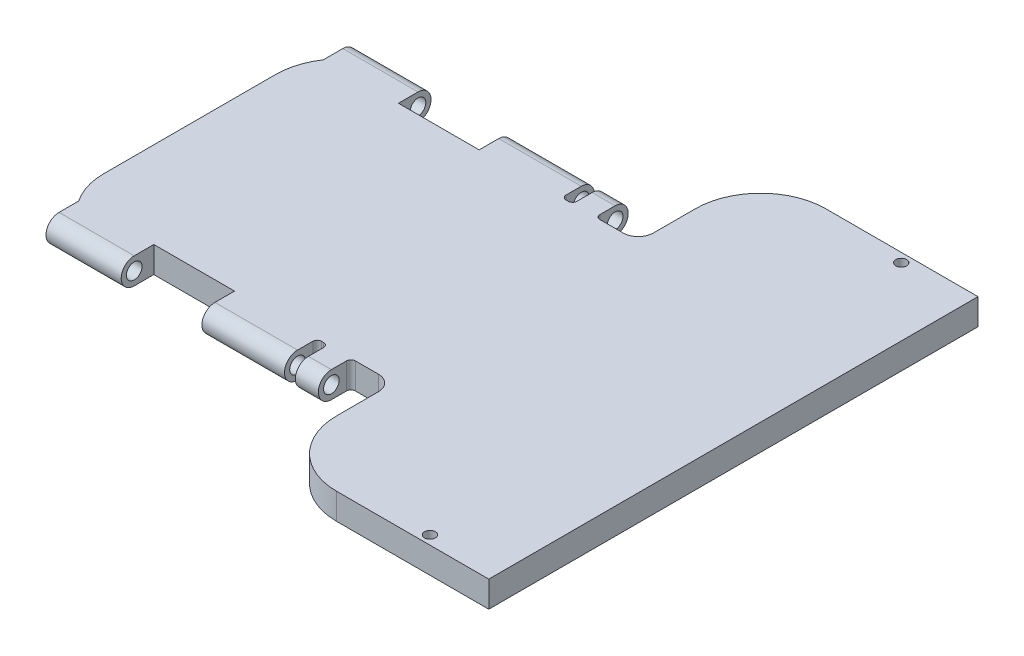
SolidWorks part; units mm, degrees
ref_plane "Front Plane" through (0, 0, 0) normal (0, 0, 1) x (1, 0, 0)
ref_plane "Top Plane" through (0, 0, 0) normal (0, 1, 0) x (1, 0, 0)
ref_plane "Right Plane" through (0, 0, 0) normal (1, 0, 0) x (0, 0, -1)
sketch "Sketch1" plane through (0, 0, 0) normal (0, 1, 0) x (1, 0, 0)
  line L0 (-120, -37.5) -> (-120, -75)
  line L1 (-120, 75) -> (0, 75)
  line L2 (-120, 75) -> (-120, 37.5)
  line L3 (-120, -75) -> (0, -75)
  line L5 (-120, 75) -> (0, 0) construction
  line L6 (0, 75) -> (0, -75)
  line L7 (-220, 37.5) -> (-120, 37.5)
  line L8 (-220, 37.5) -> (-220, -37.5)
  line L9 (-220, -37.5) -> (-120, -37.5)
  line L11 (-220, 37.5) -> (-120, -37.5) construction
  line L12 (-220, -37.5) -> (-120, 37.5) construction
  line L13 (-237.7651, 0) -> (0, 0) construction
  line L14 (0, 88.8927) -> (0, -90.7354) construction
  point P0 (0, 0)
  point P6 (-170, 0)
  dimension "D1" = 100
  dimension "D2" = 75
  dimension "D3" = 120
  dimension "D4" = 150
extrude "Boss-Extrude1" add sketch "Sketch1" along normal blind 8
ref_plane "Plane1" through (-170, 0, 0) normal (-1, 0, 0) x (0, 0, 1)
sketch "Sketch4" plane through (-170, 0, 0) normal (-1, 0, 0) x (0, 0, 1)
  line L0 (37.5, 8) -> (43.5, 8)
  line L1 (37.5, 0) -> (43.5, 0)
  line L2 (37.5, 8) -> (37.5, 0)
  line L3 (0, 17.6181) -> (0, -10.735) construction
  line L4 (-37.5, 0) -> (-43.5, 0)
  line L5 (-37.5, 8) -> (-37.5, 0)
  line L6 (-37.5, 8) -> (-43.5, 8)
  arc A0 (43.5, 0) -> (43.5, 8) centre (43.5, 4) ccw
  circle A1 centre (43.5, 4) radius 2.4
  circle A2 centre (-43.5, 4) radius 2.4
  arc A3 (-43.5, 0) -> (-43.5, 8) centre (-43.5, 4) cw
  dimension "D1" = 6
extrude "Boss-Extrude2" add sketch "Sketch4" along normal blind 46.584 and the other way blind 46.584
sketch "Sketch6" plane through (0, 0, 0) normal (1, 0, 0) x (0, 0, -1)
  line L0 (0, 15.0631) -> (0, -9.5042) construction
  line L1 (-75, 4) -> (0, 4) construction
  line L2 (-75, 8) -> (-75, 0) construction
  line L3 (-75, 8) -> (75, 8) construction
  line L4 (-60, 5.5) -> (-40, 5.5)
  line L5 (-60, 5.5) -> (-60, 2.5)
  line L6 (-60, 2.5) -> (-40, 2.5)
  line L7 (-40, 5.5) -> (-40, 2.5)
  line L8 (-60, 5.5) -> (-40, 2.5) construction
  line L9 (-60, 2.5) -> (-40, 5.5) construction
  line L10 (40, 5.5) -> (40, 2.5)
  line L11 (60, 5.5) -> (60, 2.5)
  line L12 (60, 2.5) -> (40, 2.5)
  line L13 (60, 5.5) -> (40, 5.5)
  point P7 (-50, 4)
  dimension "D1" = 2.5
  dimension "D2" = 15
  dimension "D3" = 20
extrude "Boss-Extrude3" add sketch "Sketch6" along normal blind 30
sketch "Sketch7" plane through (0, 5.5, 0) normal (0, 1, 0) x (1, 0, 0)
  line L0 (30, 60) -> (30, 40) construction
  line L1 (-120, -75) -> (0, -75) construction
  line L3 (0, -50) -> (30, -50) construction
  line L4 (0, -40) -> (0, -60) construction
  line L5 (30, -40) -> (30, -60) construction
  circle A0 centre (22.5, 50) radius 2
  circle A1 centre (22.5, -50) radius 2
  dimension "D1" = 7.5
  dimension "D2" = 25
extrude "Cut-Extrude2" cut sketch "Sketch7" against normal through all and the other way through all
sketch "Sketch8" plane through (0, 0, 0) normal (1, 0, 0) x (0, 0, -1)
  line L0 (0, 8) -> (0, 0) construction
  line L1 (-75, 8) -> (75, 8) construction
  line L3 (-20, 5.5) -> (20, 5.5)
  line L4 (-20, 5.5) -> (-20, 2.5)
  line L5 (-20, 2.5) -> (20, 2.5)
  line L6 (20, 5.5) -> (20, 2.5)
  line L7 (-20, 5.5) -> (20, 2.5) construction
  line L8 (-20, 2.5) -> (20, 5.5) construction
  point P5 (0, 4)
  dimension "D1" = 2.5
  dimension "D2" = 40
extrude "Cut-Extrude3" cut sketch "Sketch8" against normal blind 40
sketch "Sketch9" plane through (0, 8, 0) normal (0, 1, 0) x (1, 0, 0)
  line L0 (0, -75) -> (0, 75) construction
  circle A0 centre (-32.5, 0) radius 2
  dimension "D1" = 32.5
extrude "Cut-Extrude4" cut sketch "Sketch9" against normal blind 40
fillet "Fillet1" radius 20 4 edges at (-220, 4, -37.5) (-220, 4, 37.5) (-120, 4, -75) (-120, 4, 75)
sketch "Sketch10" plane through (0, 8, 0) normal (0, 1, 0) x (1, 0, 0)
  line L3 (0, 69.5) -> (-100, 69.5)
  line L4 (0, 75) -> (-100, 75)
  line L5 (0, 75) -> (-100, 75)
  line L6 (-120, 55) -> (-114.5, 55)
  line L8 (0, 75) -> (100, 75)
  line L9 (120, 55) -> (114.5, 55)
  line L10 (0, 69.5) -> (100, 69.5)
  line L11 (-88.6453, 0) -> (73.4089, 0) construction
  line L12 (0, -75) -> (100, -75)
  line L13 (120, -55) -> (114.5, -55)
  line L14 (0, -69.5) -> (100, -69.5)
  line L15 (0, -69.5) -> (-100, -69.5)
  line L16 (-120, -55) -> (-114.5, -55)
  line L17 (0, -75) -> (-100, -75)
  arc A2 (-100, 69.5) -> (-114.5, 55) centre (-100, 55) ccw
  arc A3 (-100, 75) -> (-120, 55) centre (-100, 55) ccw
  arc A4 (-100, 75) -> (-120, 55) centre (-100, 55) ccw
  arc A5 (100, 75) -> (120, 55) centre (100, 55) cw
  arc A6 (100, 69.5) -> (114.5, 55) centre (100, 55) cw
  arc A7 (100, -75) -> (120, -55) centre (100, -55) ccw
  arc A8 (100, -69.5) -> (114.5, -55) centre (100, -55) ccw
  arc A9 (-100, -69.5) -> (-114.5, -55) centre (-100, -55) cw
  arc A10 (-100, -75) -> (-120, -55) centre (-100, -55) cw
  dimension "D1" = 0
  dimension "D2" = 5.5
sketch "Sketch17" plane through (0, 8, 0) normal (0, 1, 0) x (1, 0, 0)
  line L1 (-100, 75) -> (-100, 69.5) construction
  line L2 (-100, 72.25) -> (0, 72.25) construction
  line L3 (0, -75) -> (0, 75) construction
  line L4 (0, 0) -> (-128.8243, 0) construction
  circle A0 centre (-75, 72.25) radius 1.5
  circle A1 centre (-25, 72.25) radius 1.5
  circle A2 centre (-25, -72.25) radius 1.5
  circle A3 centre (-75, -72.25) radius 1.5
  dimension "D1" = 25
  dimension "D2" = 25
extrude "Cut-Extrude10" cut sketch "Sketch17" against normal blind 25
scale "Scale1" scale about centroid uniform scaling yes scale factor 1.5
sketch "Sketch18" plane through (0, 10, 0) normal (0, 1, 0) x (1, 0, 0)
  line L0 (-132.1126, -56.25) -> (-132.1126, -82.5) construction
  line L1 (-32.1126, 151.8559) -> (160.5236, 151.8559)
  line L2 (-32.1126, 151.8559) -> (-32.1126, -145.6636)
  line L3 (-32.1126, -145.6636) -> (160.5236, -145.6636)
  line L4 (160.5236, 151.8559) -> (160.5236, -145.6636)
  dimension "D1" = 100
extrude "Cut-Extrude11" cut sketch "Sketch18" against normal through all
sketch "Sketch19" plane through (0, 0, 112.5) normal (0, 0, 1) x (1, 0, 0)
  line L0 (-137.2366, 4) -> (-164.8092, 4) construction
  line L1 (-137.2366, -2) -> (-137.2366, 10) construction
  line L2 (-137.2366, -2) -> (-276.9885, -2) construction
  line L3 (-167.3092, 10) -> (-162.3092, 10)
  line L4 (-167.3092, 10) -> (-167.3092, -2)
  line L5 (-167.3092, -2) -> (-162.3092, -2)
  line L6 (-162.3092, 10) -> (-162.3092, -2)
  line L7 (-167.3092, 10) -> (-162.3092, -2) construction
  line L8 (-167.3092, -2) -> (-162.3092, 10) construction
  dimension "D1" = 27.5726
  dimension "D2" = 5
extrude "Cut-Extrude12" cut sketch "Sketch19" against normal up to vertex (56.25 mm away) up to point (-137.2366, 10, 56.25)
mirror "Mirror2" about plane through (0, 0, 0) normal (0, 0, 1) of "Cut-Extrude12"
sketch "Sketch20" plane through (0, 10, 0) normal (0, 1, 0) x (1, 0, 0)
  line L0 (-167.3092, -60.75) -> (-205.9068, -60.75) construction
  line L2 (-167.3092, -56.25) -> (-167.3092, -65.25) construction
  line L3 (-162.3092, -56.25) -> (-167.3092, -56.25) construction
  line L4 (-205.9068, -56.25) -> (-240.9068, -56.25)
  line L5 (-205.9068, -56.25) -> (-205.9068, -76.9988)
  line L6 (-205.9068, -76.9988) -> (-240.9068, -76.9988)
  line L7 (-240.9068, -56.25) -> (-240.9068, -76.9988)
  line L8 (-167.3092, -63.8038) -> (-151.7407, -63.8038) construction
  line L10 (-151.7407, -56.25) -> (-136.2091, -56.25)
  line L11 (-151.7407, -56.25) -> (-151.7407, -73.1043)
  line L12 (-151.7407, -73.1043) -> (-136.2091, -73.1043)
  line L13 (-136.2091, -56.25) -> (-136.2091, -73.1043)
  dimension "D1" = 38.5976
  dimension "D2" = 35
extrude "Cut-Extrude13" cut sketch "Sketch20" against normal through all
fillet "Fillet2" radius 2 5 edges at (-151.7407, 4, 56.25) (-167.3092, 4, 56.25) (-162.3092, 4, 56.25) (-240.9068, 4, 56.25) (-205.9068, 4, 56.25)
mirror "Mirror3" about plane through (0, 0, 0) normal (0, 0, 1) of "Cut-Extrude13"
fillet "Fillet3" radius 7 2 edges at (-132.1126, 4, 56.25) (-132.1126, 4, -56.25)
fillet "Fillet4" radius 2 5 edges at (-151.7407, 4, -56.25) (-167.3092, 4, -56.25) (-162.3092, 4, -56.25) (-240.9068, 4, -56.25) (-205.9068, 4, -56.25)
scale "Scale2" scale about centroid uniform scaling yes scale factor 0.8
sketch "Sketch21" plane through (0, 8.8, 0) normal (0, 1, 0) x (1, 0, 0)
  circle A0 centre (-79.4935, 86.7) radius 1.8
  circle A1 centre (-79.4935, -86.7) radius 1.8
extrude "Boss-Extrude4" add sketch "Sketch21" against normal up to surface (9.6 mm away) up to face at (-79.4935, 8.8, 84.9)
sketch "Sketch22" plane through (0, 8.8, 0) normal (0, 1, 0) x (1, 0, 0)
  line L0 (-109.4935, 90) -> (-109.4935, 83.4) construction
  line L1 (-109.4935, 83.4) -> (-53.4935, 83.4) construction
  line L2 (-53.4935, 90) -> (-53.4935, -90) construction
  line L3 (-109.4935, 86.7) -> (-53.4935, 86.7) construction
  line L4 (-109.4935, -86.7) -> (-53.4935, -86.7) construction
  line L6 (-253.4935, 0) -> (-53.4935, 0) construction
  line L7 (-253.4935, 31.5851) -> (-253.4935, -31.5851) construction
  line L8 (-109.4935, -83.4) -> (-53.4935, -83.4) construction
  line L9 (-109.4935, -90) -> (-109.4935, -83.4) construction
  circle A2 centre (-78.4325, 86.7) radius 2
  circle A3 centre (-78.4325, -86.7) radius 2
  dimension "D2" = 31.061
  dimension "D1" = 6.6
extrude "Cut-Extrude14" cut sketch "Sketch22" against normal through all
sketch "Sketch23" plane through (0, 8.8, 0) normal (0, 1, 0) x (1, 0, 0)
  line L0 (-220.5289, 57) -> (-249.3943, 57) construction
  line L1 (-221.0289, 57) -> (-217.8558, 57)
  line L2 (-221.0289, 57) -> (-221.0289, 45)
  line L3 (-221.0289, 45) -> (-217.8558, 45)
  line L4 (-217.8558, 57) -> (-217.8558, 45)
  line L5 (-194.1289, 45) -> (-218.9289, 45) construction
  line L6 (-220.5289, 46.6) -> (-220.5289, 52.2) construction
  line L7 (-253.4935, 0) -> (-53.4935, 0) construction
  line L8 (-253.4935, 31.5851) -> (-253.4935, -31.5851) construction
  line L9 (-53.4935, 90) -> (-53.4935, -90) construction
  line L10 (-217.8558, -57) -> (-217.8558, -45)
  line L11 (-221.0289, -45) -> (-217.8558, -45)
  line L12 (-221.0289, -57) -> (-221.0289, -45)
  line L13 (-221.0289, -57) -> (-217.8558, -57)
  line L14 (-161.6508, 57) -> (-192.5289, 57) construction
  line L15 (-192.0289, 57) -> (-194.8929, 57)
  line L16 (-192.0289, 57) -> (-192.0289, 45)
  line L17 (-192.0289, 45) -> (-194.8929, 45)
  line L18 (-194.8929, 57) -> (-194.8929, 45)
  line L19 (-192.5289, -57) -> (-161.6508, -57) construction
  line L20 (-192.0289, -57) -> (-194.8929, -57)
  line L21 (-192.0289, -57) -> (-192.0289, -45)
  line L22 (-192.0289, -45) -> (-194.8929, -45)
  line L23 (-194.8929, -57) -> (-194.8929, -45)
  line L24 (-194.1289, -45) -> (-218.9289, -45) construction
  line L25 (-192.5289, -52.2) -> (-192.5289, -57) construction
  line L26 (-192.5289, 52.2) -> (-192.5289, 46.6) construction
  dimension "D1" = 0.5
  dimension "D2" = 0.5
  dimension "D3" = 0.5
extrude "Cut-Extrude15" cut sketch "Sketch23" against normal through all
sketch "Sketch25" plane through (0, 8.8, 0) normal (0, 1, 0) x (1, 0, 0)
  line L0 (-249.3943, -57) -> (-221.0289, -57) construction
  line L1 (-221.7289, -57) -> (-218.2616, -57)
  line L2 (-221.7289, -57) -> (-221.7289, -45)
  line L3 (-221.7289, -45) -> (-218.2616, -45)
  line L4 (-218.2616, -57) -> (-218.2616, -45)
  line L5 (-192.0289, -45) -> (-221.0289, -45) construction
  line L6 (-221.0289, 57) -> (-249.3943, 57) construction
  line L7 (-221.7289, 57) -> (-218.2616, 57)
  line L8 (-221.7289, 57) -> (-221.7289, 45)
  line L9 (-221.7289, 45) -> (-218.2616, 45)
  line L10 (-218.2616, 57) -> (-218.2616, 45)
  line L11 (-192.0289, 45) -> (-221.0289, 45) construction
  line L12 (-221.0289, 52.2) -> (-221.0289, 45) construction
  line L13 (-221.0289, -57) -> (-221.0289, -52.2) construction
  dimension "D1" = 0.7
  dimension "D2" = 0.7
extrude "Cut-Extrude17" cut sketch "Sketch25" against normal through all
